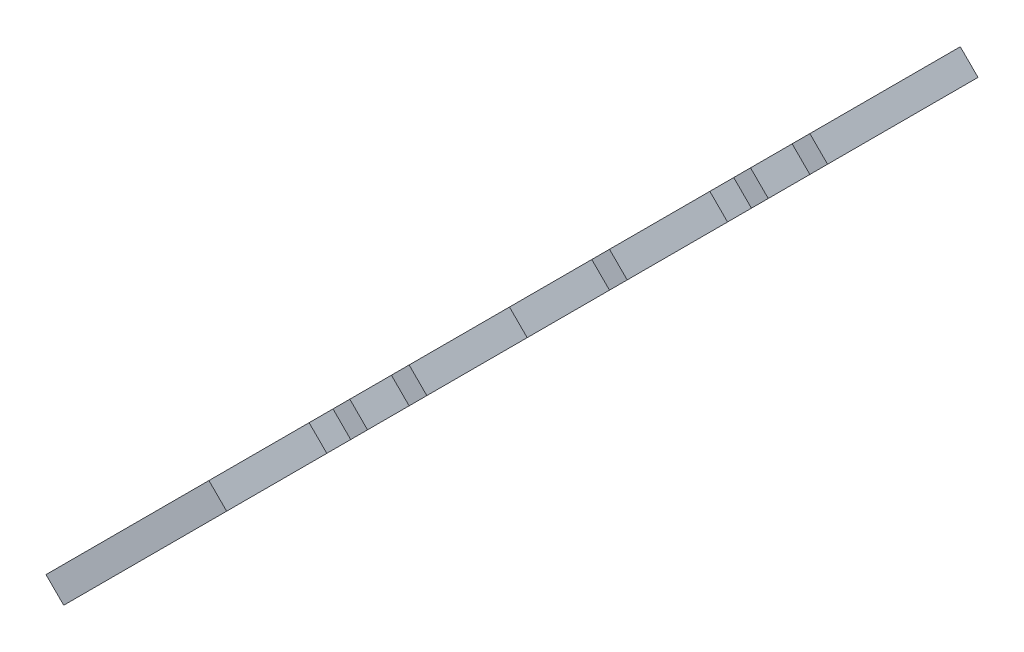
SolidWorks part; units mm, degrees
ref_plane "Front Plane" through (0, 0, 0) normal (0, 0, 1) x (1, 0, 0)
ref_plane "Top Plane" through (0, 0, 0) normal (0, 1, 0) x (1, 0, 0)
ref_plane "Right Plane" through (0, 0, 0) normal (1, 0, 0) x (0, 0, -1)
sketch "Sketch1" plane through (0, 0, 0) normal (0, 0, 1) x (1, 0, 0)
  line L0 (-108.2121, 4.5408) -> (-66.9029, 45.85)
  line L1 (-108.2121, 4.5408) -> (-112.7022, 9.0309)
  line L2 (-66.9029, 45.85) -> (-71.393, 50.3401)
  line L3 (-112.7022, 9.0309) -> (-71.393, 50.3401)
  line L4 (-76.7812, -26.8901) -> (-72.2911, -22.4) construction
extrude "Boss-Extrude1" add sketch "Sketch1" along normal up to surface (190.5 mm away)
sketch "Sketch2" plane through (-60.8666, 60.8666, 0) normal (-0.7071, 0.7071, 0) x (0, 0, 1)
  line L0 (190.5, -14.8867) -> (0, -14.8867) construction
  line L1 (165.1, -21.2367) -> (139.7412, -21.2367)
  line L2 (165.1, -21.2367) -> (165.1, -14.8867)
  line L3 (165.1, -14.8867) -> (139.7412, -14.8867)
  line L4 (139.7412, -21.2367) -> (139.7412, -14.8867)
  line L5 (190.5, -73.3067) -> (0, -73.3067) construction
  line L6 (165.1, -66.9567) -> (139.7412, -66.9567)
  line L7 (165.1, -66.9567) -> (165.1, -73.3067)
  line L8 (165.1, -73.3067) -> (139.7412, -73.3067)
  line L9 (139.7412, -66.9567) -> (139.7412, -73.3067)
  dimension "D1" = 25.3588
extrude "Cut-Extrude1" cut sketch "Sketch2" against normal blind 6.35
pattern_linear "LPattern1" count 3 spacing 50.8 along (0, 0, -1) of "Cut-Extrude1"
sketch "Sketch3" plane through (0, 0, 0) normal (0, 0, -1) x (-1, 0, 0)
  line L0 (92.4966, 20.2562) -> (96.9868, 24.7464)
  line L1 (108.2121, 4.5408) -> (66.9029, 45.85) construction
  line L2 (71.393, 50.3401) -> (112.7022, 9.0309) construction
  line L3 (96.9868, 24.7464) -> (88.0065, 33.7266)
  line L4 (88.0065, 33.7266) -> (83.5144, 29.2385)
  line L5 (187.6134, 29.2385) -> (16.1634, 29.2385) construction
  line L6 (83.5144, 29.2385) -> (92.4966, 20.2562)
  dimension "D1" = 12.7
  dimension "D2" = 6.35
  dimension "D3" = 22.225
extrude "Boss-Extrude2" add sketch "Sketch3" along normal blind 6.35
sketch "Sketch5" plane through (-56.3764, 56.3764, 0) normal (0.7071, -0.7071, 0) x (0, 0, -1)
  line L0 (-179.9336, -73.3067) -> (-175.6664, -66.9567) construction
  line L1 (-190.5, -73.3067) -> (-165.1, -73.3067) construction
  line L2 (-179.9336, -66.9567) -> (-179.9336, -73.3067) construction
  line L3 (-175.6664, -73.3067) -> (-179.9336, -66.9567) construction
  line L4 (-175.6664, -66.9567) -> (-175.6664, -73.3067) construction
  line L5 (-78.3336, -73.3067) -> (-74.0664, -66.9567) construction
  line L6 (-88.9412, -73.3067) -> (-63.5, -73.3067) construction
  line L7 (-78.3336, -66.9567) -> (-78.3336, -73.3067) construction
  line L8 (-74.0664, -73.3067) -> (-78.3336, -66.9567) construction
  line L9 (-74.0664, -66.9567) -> (-74.0664, -73.3067) construction
  line L10 (-18.0086, -73.3067) -> (-13.7414, -66.9567) construction
  line L11 (-38.1412, -73.3067) -> (0, -73.3067) construction
  line L12 (-18.0086, -66.9567) -> (-18.0086, -73.3067) construction
  line L13 (-13.7414, -73.3067) -> (-18.0086, -66.9567) construction
  line L14 (-13.7414, -66.9567) -> (-13.7414, -73.3067) construction
  circle A0 centre (-177.8, -70.1317) radius 2.0955
  circle A1 centre (-76.2, -70.1317) radius 2.0955
  circle A2 centre (-15.875, -70.1317) radius 2.0955
  dimension "D1" = 4.191
extrude "Cut-Extrude2" cut sketch "Sketch5" against normal through all
ref_plane "Midplane" through (-31.1811, -31.1811, 0) normal (-0.7071, -0.7071, 0) x (-0.7071, 0.7071, 0)
mirror "Mirror1" about plane through (-31.1811, -31.1811, 0) normal (-0.7071, -0.7071, 0) of "Cut-Extrude2"
sketch "Sketch6" plane through (-60.8666, 60.8666, 0) normal (-0.7071, 0.7071, 0) x (0, 0, 1)
  line L0 (152.4206, -3.6091) -> (152.4206, -40.9822) construction
  line L1 (139.7412, -14.8867) -> (139.7412, -21.2367) construction
  line L2 (165.1, -21.2367) -> (165.1, -14.8867) construction
  line L3 (50.8206, 6.6062) -> (50.8206, -35.0025) construction
  line L4 (38.1412, -14.8867) -> (38.1412, -21.2367) construction
  line L5 (63.5, -21.2367) -> (63.5, -14.8867) construction
  line L7 (38.1412, -21.2367) -> (63.5, -21.2367) construction
  line L11 (139.7412, -21.2367) -> (165.1, -21.2367) construction
  line B0 (52.9542, -21.2367) -> (48.687, -21.2367)
  line B1 (48.687, -33.1747) -> (46.3756, -33.1747)
  line B2 (46.3756, -33.1747) -> (46.3756, -29.9997)
  line B3 (46.3756, -29.9997) -> (48.687, -29.9997)
  line B4 (48.687, -29.9997) -> (48.687, -21.2367)
  line B5 (48.687, -33.1747) -> (48.687, -36.4767)
  line B6 (48.687, -36.4767) -> (52.9542, -36.4767)
  line B7 (52.9542, -33.1747) -> (52.9542, -36.4767)
  line B8 (52.9542, -29.9997) -> (52.9542, -21.2367)
  line B9 (55.2656, -29.9997) -> (52.9542, -29.9997)
  line B10 (55.2656, -33.1747) -> (55.2656, -29.9997)
  line B11 (52.9542, -33.1747) -> (55.2656, -33.1747)
  line B12 (154.5542, -21.2367) -> (150.287, -21.2367)
  line B13 (150.287, -33.1747) -> (147.9756, -33.1747)
  line B14 (147.9756, -33.1747) -> (147.9756, -29.9997)
  line B15 (147.9756, -29.9997) -> (150.287, -29.9997)
  line B16 (150.287, -29.9997) -> (150.287, -21.2367)
  line B17 (150.287, -33.1747) -> (150.287, -36.4767)
  line B18 (150.287, -36.4767) -> (154.5542, -36.4767)
  line B19 (154.5542, -33.1747) -> (154.5542, -36.4767)
  line B20 (154.5542, -29.9997) -> (154.5542, -21.2367)
  line B21 (156.8656, -29.9997) -> (154.5542, -29.9997)
  line B22 (156.8656, -33.1747) -> (156.8656, -29.9997)
  line B23 (154.5542, -33.1747) -> (156.8656, -33.1747)
sketch_block_instance "TSlot-1"
sketch_block "TSlot" parameters "D1"=3.302, "D2"=3.175
sketch_block_instance "TSlot-2"
extrude "Cut-Extrude3" cut sketch "Sketch6" against normal through all
mirror "Mirror2" about plane through (-31.1811, -31.1811, 0) normal (-0.7071, -0.7071, 0) of "Cut-Extrude3"
